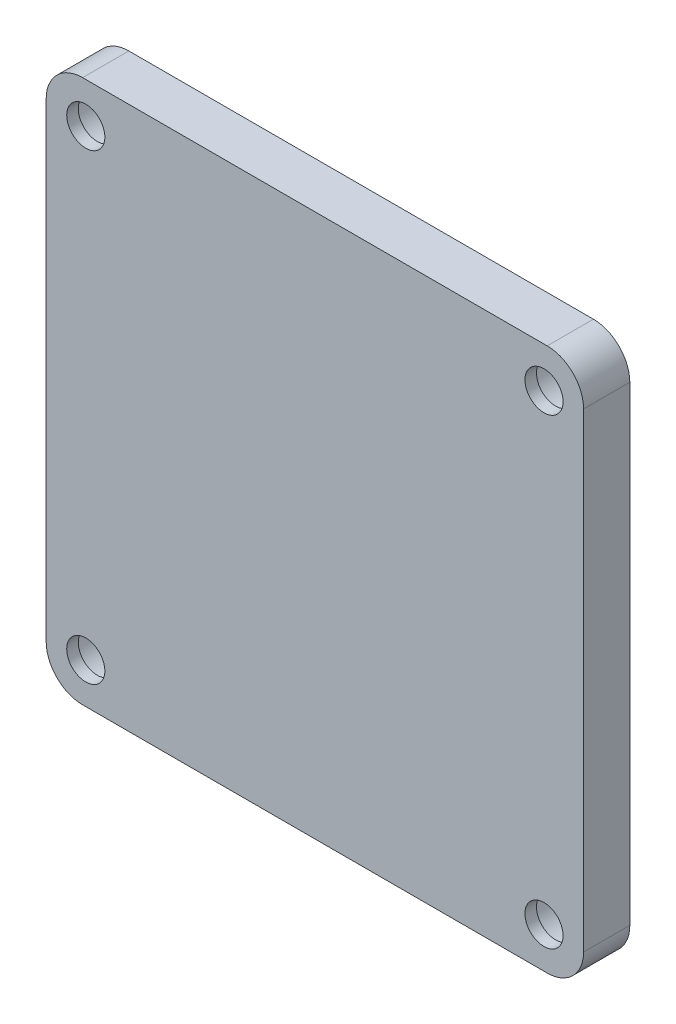
SolidWorks part; units mm, degrees
ref_plane "Plan de face" through (0, 0, 0) normal (0, 0, 1) x (1, 0, 0)
ref_plane "Plan de dessus" through (0, 0, 0) normal (0, 1, 0) x (1, 0, 0)
ref_plane "Plan de droite" through (0, 0, 0) normal (1, 0, 0) x (0, 0, -1)
sketch "Esquisse1" plane through (0, 0, 0) normal (0, 0, 1) x (1, 0, 0)
  line L0 (0, 86.6441) -> (0, -102.9786) construction
  line L1 (-46.5, 47) -> (46.5, 47)
  line L2 (-46.5, 47) -> (-46.5, -47)
  line L3 (-46.5, -47) -> (46.5, -47)
  line L4 (46.5, 47) -> (46.5, -47)
  line L5 (117.1826, 0) -> (-117.5377, 0) construction
  line L6 (-39.65, -40) -> (39.65, -40) construction
  line L7 (39.65, -40) -> (39.65, 40) construction
  line L8 (39.65, 40) -> (-39.65, 40) construction
  line L9 (-39.65, 40) -> (-39.65, -40) construction
  point P11 (0, -40)
  point P14 (-39.65, 0)
  dimension "D1" = 94
  dimension "D2" = 93
  dimension "D3" = 80
  dimension "D4" = 79.3
extrude "Extrusion1" add sketch "Esquisse1" along normal blind 8
fillet "Congé1" radius 6.3 4 edges at (46.5, -47, 4) (-46.5, -47, 4) (-46.5, 47, 4) (46.5, 47, 4)
ref_point "Point1"
ref_point "Point2"
ref_point "Point3"
ref_point "Point4"
hole_wizard "Chambrage pour vis à tête hexagonale M61" positions "Esquisse9" profile "Esquisse8" counterbore size "M6" standard "ISO" end condition through all
sketch "Esquisse9" plane through (0, 0, 0) normal (0, 0, -1) x (-1, 0, 0)
  point P1 (39.65, -40)
  point P4 (39.65, 40)
  point P7 (-39.65, 40)
  point P10 (-39.65, -40)
sketch "Esquisse8" plane through (-39.65, -40, 0) normal (1, 0, 0) x (0, 1, 0)
  line L0 (0, 0) -> (0, 8)
  line L1 (0, 8) -> (3.3, 8)
  line L3 (3.3, 8) -> (3.3, 6)
  line L4 (3.3, 6) -> (5.5, 6)
  line L5 (5.5, 6) -> (5.5, 0)
  line L7 (5.5, 0) -> (0, 0)
  line L11 (0, -6.35) -> (0, 107.95) construction
  dimension "Diamètre du perçage jusqu'au prochain" = 6.6
  dimension "Profondeur du perçage jusqu'au prochain" = 8
  dimension "Diamètre du chambrage" = 11
  dimension "Profondeur du chambrage" = 6
sketch "Esquisse10" plane through (0, 0, 0) normal (0, 0, -1) x (-1, 0, 0)
  line L0 (0, 0) -> (0, 42.4139) construction
  line L1 (-20, 35.3046) -> (20, 35.3046)
  line L2 (-20, 35.3046) -> (-20, 10.3046)
  line L3 (-20, 10.3046) -> (20, 10.3046)
  line L4 (20, 35.3046) -> (20, 10.3046)
  line L5 (0, 42.4139) -> (0, 0) construction
  line L6 (0, 0) -> (26.3566, 0) construction
  dimension "D1" = 25
  dimension "D2" = 40
extrude "Enlèv. mat.-Extru.1" cut sketch "Esquisse10" against normal blind 2
fillet "Congé2" radius 2 4 edges at (0, 35.3046, 2) (-20, 22.8046, 2) (0, 10.3046, 2) (20, 22.8046, 2)
